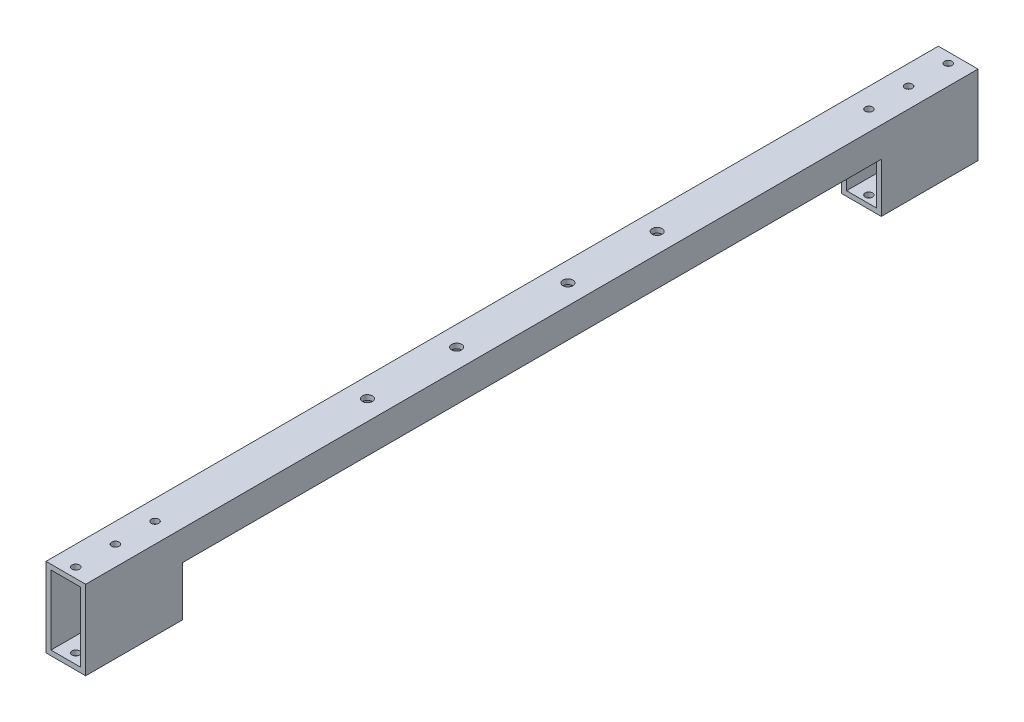
SolidWorks part; units mm, degrees
material "6061-T6 (SS)"
ref_plane "Front Plane" through (0, 0, 0) normal (0, 0, 1) x (1, 0, 0)
ref_plane "Top Plane" through (0, 0, 0) normal (0, 1, 0) x (1, 0, 0)
ref_plane "Right Plane" through (0, 0, 0) normal (1, 0, 0) x (0, 0, -1)
sketch "Sketch1" plane through (0, 0, 0) normal (0, 0, 1) x (1, 0, 0)
  line L1 (-12.7, -25.4) -> (12.7, -25.4)
  line L2 (-12.7, -25.4) -> (-12.7, 25.4)
  line L3 (-12.7, 25.4) -> (12.7, 25.4)
  line L4 (12.7, -25.4) -> (12.7, 25.4)
  line L5 (-12.7, -25.4) -> (12.7, 25.4) construction
  line L6 (-12.7, 25.4) -> (12.7, -25.4) construction
  point P0 (0, 0)
  dimension "D1" = 50.8
  dimension "D2" = 25.4
extrude "Extrude-Thin1" add sketch "Sketch1" along normal blind 571.5 thin thin type one direction reverse wall 3.175
hole_wizard "3/16 (0.1875) Diameter Hole1" positions "3DSketch1" profile "Sketch3" hole size "3/16" standard "ANSI Inch" end condition through all
sketch3d "3DSketch1"
  line L1 (12.7, 25.4, 0) -> (-12.7, 25.4, 0) construction
  line L6 (0, 25.4, 571.5) -> (0, 25.4, 0) construction
  line L7 (12.7, 25.4, 571.5) -> (-12.7, 25.4, 571.5) construction
  point P57 (0, 25.4, 6.35)
  point P59 (0, 25.4, 31.75)
  point P61 (0, 25.4, 57.15)
  point P63 (0, 25.4, 539.75)
  point P65 (0, 25.4, 514.35)
  point P67 (0, 25.4, 565.15)
  dimension "D1" = 25.4
  dimension "D2" = 25.4
  dimension "D3" = 6.35
  dimension "D4" = 25.4
  dimension "D5" = 25.4
  dimension "D6" = 6.35
sketch "Sketch3" plane through (0, 25.4, 565.15) normal (1, 0, 0) x (0, 0, 1)
  line L0 (0, 0) -> (0, 50.8)
  line L1 (0, 50.8) -> (2.3812, 50.8)
  line L2 (2.3812, 50.8) -> (2.3812, 0)
  line L5 (2.3812, 0) -> (0, 0)
  line L11 (0, -6.35) -> (0, 107.95) construction
  dimension "Thru Hole Dia." = 4.7625
  dimension "Thru Hole Depth" = 50.8
hole_wizard "1/4 (0.25) Diameter Hole1" positions "Sketch6" profile "Sketch7" hole size "1/4" standard "ANSI Inch" end condition through all
sketch "Sketch6" plane through (0, 25.4, 0) normal (0, 1, 0) x (1, 0, 0)
  point P0 (0, -321.183)
  point P3 (0, -378.333)
  point P6 (0, -192.786)
  point P9 (0, -249.936)
sketch "Sketch7" plane through (0, 25.4, 321.183) normal (1, 0, 0) x (0, 0, 1)
  line L0 (0, 0) -> (0, 50.8)
  line L1 (0, 50.8) -> (3.175, 50.8)
  line L2 (3.175, 50.8) -> (3.175, 0)
  line L5 (3.175, 0) -> (0, 0)
  line L11 (0, -6.35) -> (0, 107.95) construction
  dimension "Thru Hole Dia." = 6.35
  dimension "Thru Hole Depth" = 50.8
sketch "Sketch10" plane through (12.7, 0, 0) normal (1, 0, 0) x (0, 0, -1)
  line L0 (-509.5748, -25.4) -> (-509.5748, 6.35)
  line L2 (-571.5, -25.4) -> (0, -25.4) construction
  line L3 (-509.5748, 6.35) -> (-61.9252, 6.35)
  line L4 (-61.9252, 6.35) -> (-61.9252, -25.4)
  line L5 (-285.75, -25.4) -> (-285.75, 6.35) construction
  line L6 (-509.5748, -25.4) -> (-61.9252, -25.4)
  dimension "D1" = 447.6496
  dimension "D2" = 31.75
extrude "Cut-Extrude1" cut sketch "Sketch10" against normal through all
